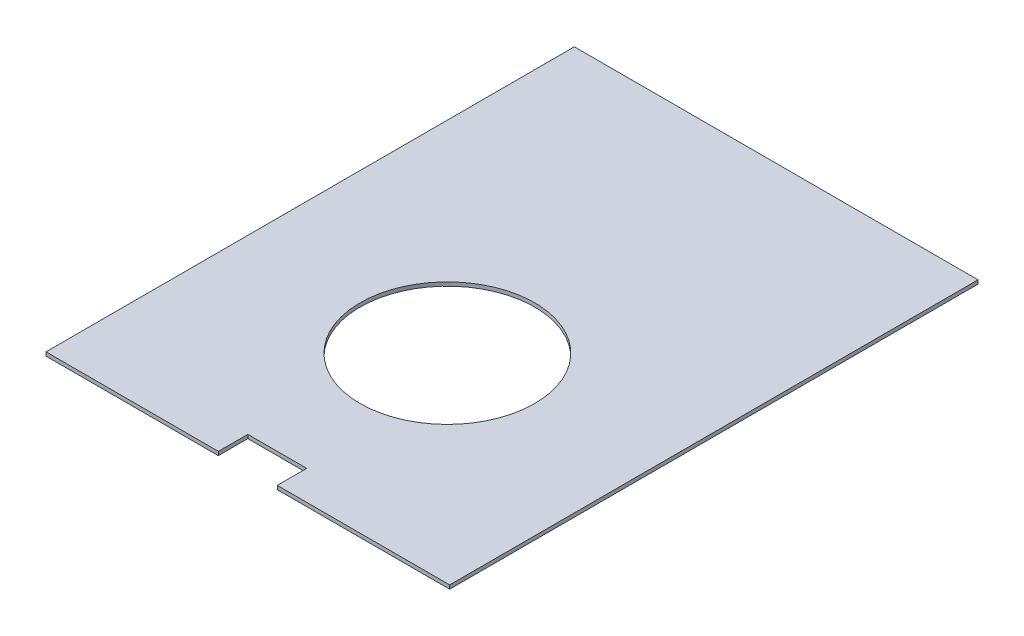
SolidWorks part; units mm, degrees
ref_plane "Front Plane" through (0, 0, 0) normal (0, 0, 1) x (1, 0, 0)
ref_plane "Top Plane" through (0, 0, 0) normal (0, 1, 0) x (1, 0, 0)
ref_plane "Right Plane" through (0, 0, 0) normal (1, 0, 0) x (0, 0, -1)
sketch "Sketch4" plane through (0, 0, 0) normal (0, 1, 0) x (1, 0, 0)
  line L1 (-190.5, -254) -> (190.5, -254)
  line L2 (-190.5, -254) -> (-190.5, 254)
  line L3 (-190.5, 254) -> (190.5, 254)
  line L4 (190.5, -254) -> (190.5, 254)
  line L5 (-190.5, -254) -> (190.5, 254) construction
  line L6 (-190.5, 254) -> (190.5, -254) construction
  point P0 (0, 0)
  point P5 (0, 0)
  point P6 (0, 0)
  point P7 (0, 0)
extrude "Boss-Extrude1" add sketch "Sketch4" along normal blind 3.81
sketch "Sketch7" plane through (0, 3.81, 0) normal (0, 1, 0) x (1, 0, 0)
  line L1 (-205.5, -269) -> (205.5, -269)
  line L2 (-205.5, -269) -> (-205.5, 269)
  line L3 (-205.5, 269) -> (205.5, 269)
  line L4 (190.5, -254) -> (190.5, 254)
  line L5 (190.5, 254) -> (-190.5, 254)
  line L6 (-190.5, 254) -> (-190.5, -254)
  line L7 (-190.5, -254) -> (190.5, -254)
  line L8 (190.5, -254) -> (190.5, 254)
  line L9 (190.5, 254) -> (-190.5, 254)
  line L10 (-190.5, 254) -> (-190.5, -254)
  line L11 (-190.5, -254) -> (190.5, -254)
  line L12 (205.5, -269) -> (205.5, 269)
  line L13 (-205.5, -269) -> (205.5, 269) construction
  line L14 (-205.5, 269) -> (205.5, -269) construction
  point P2 (0, 0)
  dimension "D2" = 15
  dimension "D3" = 15
  dimension "D1" = 0
extrude "Boss-Extrude2" add sketch "Sketch7" against normal up to surface (3.81 mm away) up to face at (0, 0, 0)
sketch "Sketch5" plane through (0, 3.81, 0) normal (0, 1, 0) x (1, 0, 0)
  line L0 (0, -269) -> (0, -65.8) construction
  line L2 (-205.5, -269) -> (205.5, -269) construction
  circle A0 centre (0, -65.8) radius 88.9
  point P2 (0, 0)
  point P5 (0, -4.3276)
  dimension "D1" = 177.8
  dimension "D2" = 203.2
extrude "Cut-Extrude1" cut sketch "Sketch5" against normal through all
sketch "Sketch6" plane through (0, 3.81, 0) normal (0, 1, 0) x (1, 0, 0)
  line L1 (0, 0) -> (0, -239) construction
  line L2 (-30, -269) -> (30, -269)
  line L3 (-30, -269) -> (-30, -239)
  line L4 (-30, -239) -> (30, -239)
  line L5 (30, -269) -> (30, -239)
  line L6 (-205.5, -269) -> (205.5, -269) construction
  point P0 (2.4627, -224.9979)
  dimension "D1" = 60
  dimension "D2" = 30
extrude "Cut-Extrude2" cut sketch "Sketch6" against normal through all
